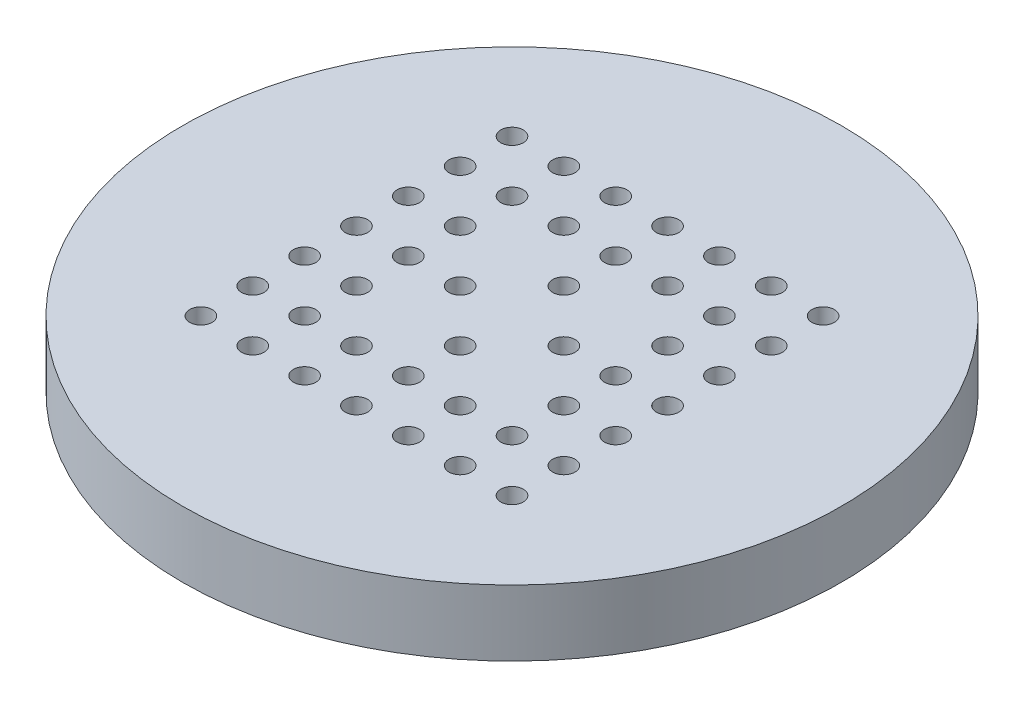
SolidWorks part; units mm, degrees
ref_plane "Front Plane" through (0, 0, 0) normal (0, 0, 1) x (1, 0, 0)
ref_plane "Top Plane" through (0, 0, 0) normal (0, 1, 0) x (1, 0, 0)
ref_plane "Right Plane" through (0, 0, 0) normal (1, 0, 0) x (0, 0, -1)
ref_axis "Axial" through (0, -55, 0) along (0, 1, 0)
ref_plane "Bottom Plane" through (0, -3.81, 0) normal (0, 1, 0) x (1, 0, 0)
sketch "Sketch1" plane through (0, 0, 0) normal (0, 1, 0) x (1, 0, 0)
  circle A0 centre (0, 0) radius 19.05
  dimension "D1" = 38.1
extrude "Billet" add sketch "Sketch1" against normal blind 3.81
sketch "Sketch2" plane through (0, 0, 0) normal (0, 1, 0) x (1, 0, 0)
  line L0 (0, 18.6449) -> (0, -20.0163) construction
  line L1 (-17.698, 0) -> (15.8694, 0) construction
  circle A0 centre (8.9916, 8.9916) radius 0.6477
  dimension "D1" = 1.2954
  dimension "D2" = 8.9916
  dimension "D3" = 8.9916
extrude "First Lox Hole" cut sketch "Sketch2" against normal through all and the other way through all contours A0
chamfer "Braising Chamfer" distance 0.254 angle 45 1 edges at (8.9916, -3.81, -8.3439)
pattern_linear "Lox Hole Pattern" count 7 spacing 2.9972 along (-1, 0, 0) count 7 spacing 2.9972 along (0, 0, 1) skipping (2, 2), (2, 4), (3, 3), (4, 2), (4, 4) of "First Lox Hole", "Braising Chamfer"
